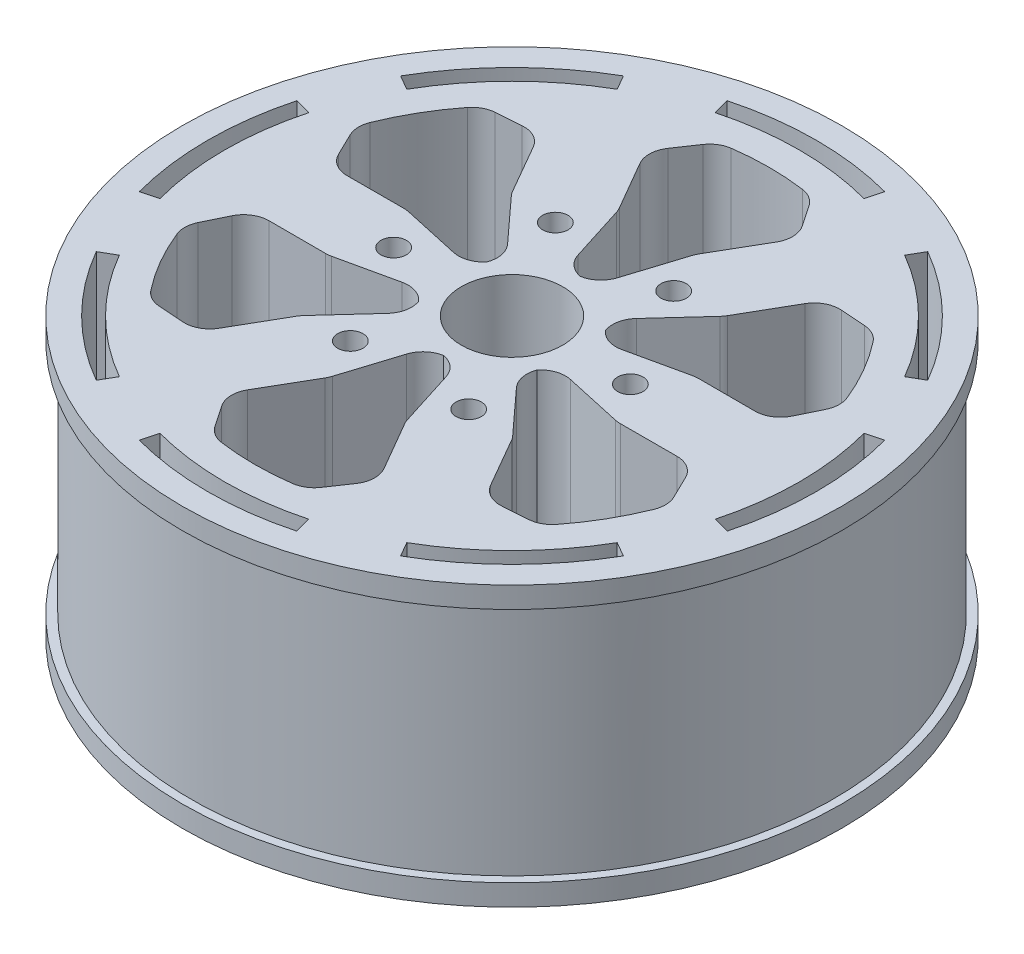
SolidWorks part; units mm, degrees
material "环氧树脂,未充填"
ref_plane "前视基准面" through (0, 0, 0) normal (0, 0, 1) x (1, 0, 0)
ref_plane "上视基准面" through (0, 0, 0) normal (0, 1, 0) x (1, 0, 0)
ref_plane "右视基准面" through (0, 0, 0) normal (1, 0, 0) x (0, 0, -1)
other "Configuration Table"
sketch "草图1" plane through (0, 0, 0) normal (0, 1, 0) x (1, 0, 0)
  circle A1 centre (0, 0) radius 38
extrude "凸台-拉伸1" add sketch "草图1" along normal blind 33
sketch "草图8" plane through (0, 0, 0) normal (0, -1, 0) x (1, 0, 0)
  circle A0 centre (0, 0) radius 39
extrude "凸台-拉伸2" add sketch "草图8" against normal blind 2.5
sketch "草图9" plane through (0, 33, 0) normal (0, 1, 0) x (1, 0, 0)
  circle A0 centre (0, 0) radius 39
extrude "凸台-拉伸3" add sketch "草图9" against normal blind 2.5
sketch "草图2" plane through (0, 0, 0) normal (0, -1, 0) x (1, 0, 0)
  circle A0 centre (0, 0) radius 32.5
extrude "切除-拉伸1" cut sketch "草图2" against normal blind 15.2
sketch "草图3" plane through (0, 33, 0) normal (0, 1, 0) x (1, 0, 0)
  line L0 (239.7439, 493.986) -> (1239.7439, 493.986) construction
  line L1 (0, 8) -> (0, 29.9069) construction
  line L3 (-5.5562, 29.9248) -> (-9.0065, 24.8288)
  line L6 (5.5562, 29.9248) -> (9.0065, 24.8288)
  line L45 (-1.6237, 7.8955) -> (-4.546, 17.1272)
  line L46 (-4.546, 17.1272) -> (-9.0065, 24.8288)
  line L47 (4.546, 17.1272) -> (9.0065, 24.8288)
  line L48 (1.6237, 7.8955) -> (4.546, 17.1272)
  line L49 (17.1056, 4.6266) -> (26.0056, 4.6146)
  line L50 (28.6937, 10.1506) -> (26.0056, 4.6146)
  line L52 (23.1376, 19.7742) -> (16.9991, 20.2143)
  line L53 (12.5596, 12.5006) -> (16.9991, 20.2143)
  line L54 (6.0258, 5.3539) -> (12.5596, 12.5006)
  line L55 (7.6496, 2.5416) -> (17.1056, 4.6266)
  line L56 (12.5596, -12.5006) -> (16.9991, -20.2143)
  line L57 (23.1376, -19.7742) -> (16.9991, -20.2143)
  line L59 (28.6937, -10.1506) -> (26.0056, -4.6146)
  line L60 (17.1056, -4.6266) -> (26.0056, -4.6146)
  line L61 (7.6496, -2.5416) -> (17.1056, -4.6266)
  line L62 (6.0258, -5.3539) -> (12.5596, -12.5006)
  line L63 (-4.546, -17.1272) -> (-9.0065, -24.8288)
  line L64 (-5.5562, -29.9248) -> (-9.0065, -24.8288)
  line L66 (5.5562, -29.9248) -> (9.0065, -24.8288)
  line L67 (4.546, -17.1272) -> (9.0065, -24.8288)
  line L68 (1.6237, -7.8955) -> (4.546, -17.1272)
  line L69 (-1.6237, -7.8955) -> (-4.546, -17.1272)
  line L70 (-17.1056, -4.6266) -> (-26.0056, -4.6146)
  line L71 (-28.6937, -10.1506) -> (-26.0056, -4.6146)
  line L73 (-23.1376, -19.7742) -> (-16.9991, -20.2143)
  line L74 (-12.5596, -12.5006) -> (-16.9991, -20.2143)
  line L75 (-6.0258, -5.3539) -> (-12.5596, -12.5006)
  line L76 (-7.6496, -2.5416) -> (-17.1056, -4.6266)
  line L77 (-12.5596, 12.5006) -> (-16.9991, 20.2143)
  line L78 (-23.1376, 19.7742) -> (-16.9991, 20.2143)
  line L80 (-28.6937, 10.1506) -> (-26.0056, 4.6146)
  line L81 (-17.1056, 4.6266) -> (-26.0056, 4.6146)
  line L82 (-7.6496, 2.5416) -> (-17.1056, 4.6266)
  line L83 (-6.0258, 5.3539) -> (-12.5596, 12.5006)
  circle A4 centre (0, 0) radius 32.35 construction
  arc A10 (1.6237, 7.8955) -> (-1.6237, 7.8955) centre (0, 0) ccw
  circle A11 centre (0, 0) radius 6
  arc A12 (7.6496, 2.5416) -> (6.0258, 5.3539) centre (0, 0) ccw
  arc A13 (6.0258, -5.3539) -> (7.6496, -2.5416) centre (0, 0) ccw
  arc A14 (-1.6237, -7.8955) -> (1.6237, -7.8955) centre (0, 0) ccw
  arc A15 (-7.6496, -2.5416) -> (-6.0258, -5.3539) centre (0, 0) ccw
  arc A16 (-6.0258, 5.3539) -> (-7.6496, 2.5416) centre (0, 0) ccw
  arc A17 (-23.1376, 19.7742) -> (-28.6937, 10.1506) centre (0, 0) ccw
  arc A18 (-28.6937, -10.1506) -> (-23.1376, -19.7742) centre (0, 0) ccw
  arc A19 (-5.5562, -29.9248) -> (5.5562, -29.9248) centre (0, 0) ccw
  arc A20 (23.1376, -19.7742) -> (28.6937, -10.1506) centre (0, 0) ccw
  arc A21 (28.6937, 10.1506) -> (23.1376, 19.7742) centre (0, 0) ccw
  arc A22 (5.5562, 29.9248) -> (-5.5562, 29.9248) centre (0, 0) ccw
  circle A31 centre (-7, 12.1244) radius 1.5
  circle A32 centre (7, 12.1244) radius 1.5
  circle A33 centre (14, 0) radius 1.5
  circle A34 centre (7, -12.1244) radius 1.5
  circle A35 centre (-7, -12.1244) radius 1.5
  circle A36 centre (-14, 0) radius 1.5
  point P8 (0.0448, 0.0448)
  point P23 (0, 29.9248)
  point P67 (0.0399, 0.0329)
  point P68 (0, 0)
  point P74 (0, 0)
  point P82 (0, 0)
  dimension "D1" = 6
  dimension "D2" = 6
extrude "切除-拉伸2" cut sketch "草图3" against normal through all
ref_axis "基准轴2" through (0, 15.2, 0) along (0, 1, 0)
sketch "草图7" plane through (0, 0, 0) normal (0, -1, 0) x (1, 0, 0)
  line L0 (-8.7998, 32.8415) -> (-9.3175, 34.7733)
  line L1 (0, 0) -> (0, 43.8624) construction
  line L2 (8.7998, 32.8415) -> (9.3175, 34.7733)
  line L3 (17, 29.4449) -> (18, 31.1769)
  line L4 (29.4449, 17) -> (31.1769, 18)
  line L5 (32.8415, 8.7998) -> (34.7733, 9.3175)
  line L6 (32.8415, -8.7998) -> (34.7733, -9.3175)
  line L7 (29.4449, -17) -> (31.1769, -18)
  line L8 (17, -29.4449) -> (18, -31.1769)
  line L9 (8.7998, -32.8415) -> (9.3175, -34.7733)
  line L10 (-8.7998, -32.8415) -> (-9.3175, -34.7733)
  line L11 (-17, -29.4449) -> (-18, -31.1769)
  line L12 (-29.4449, -17) -> (-31.1769, -18)
  line L13 (-32.8415, -8.7998) -> (-34.7733, -9.3175)
  line L14 (-32.8415, 8.7998) -> (-34.7733, 9.3175)
  line L15 (-29.4449, 17) -> (-31.1769, 18)
  line L16 (-17, 29.4449) -> (-18, 31.1769)
  arc A0 (8.7998, 32.8415) -> (-8.7998, 32.8415) centre (0, 0) ccw
  arc A1 (9.3175, 34.7733) -> (-9.3175, 34.7733) centre (0, 0) ccw
  arc A2 (29.4449, 17) -> (17, 29.4449) centre (0, 0) ccw
  arc A3 (31.1769, 18) -> (18, 31.1769) centre (0, 0) ccw
  arc A4 (32.8415, -8.7998) -> (32.8415, 8.7998) centre (0, 0) ccw
  arc A5 (34.7733, -9.3175) -> (34.7733, 9.3175) centre (0, 0) ccw
  arc A6 (17, -29.4449) -> (29.4449, -17) centre (0, 0) ccw
  arc A7 (18, -31.1769) -> (31.1769, -18) centre (0, 0) ccw
  arc A8 (-8.7998, -32.8415) -> (8.7998, -32.8415) centre (0, 0) ccw
  arc A9 (-9.3175, -34.7733) -> (9.3175, -34.7733) centre (0, 0) ccw
  arc A10 (-29.4449, -17) -> (-17, -29.4449) centre (0, 0) ccw
  arc A11 (-31.1769, -18) -> (-18, -31.1769) centre (0, 0) ccw
  arc A12 (-32.8415, 8.7998) -> (-32.8415, -8.7998) centre (0, 0) ccw
  arc A13 (-34.7733, 9.3175) -> (-34.7733, -9.3175) centre (0, 0) ccw
  arc A14 (-17, 29.4449) -> (-29.4449, 17) centre (0, 0) ccw
  arc A15 (-18, 31.1769) -> (-31.1769, 18) centre (0, 0) ccw
  point P39 (0, 0)
  dimension "D1" = 8
extrude "切除-拉伸3" cut sketch "草图7" against normal through all
fillet "圆角5" radius 3 48 edges at (7.6496, 24.1, -2.5416) (6.0258, 24.1, -5.3539) (12.5596, 24.1, -12.5006) (16.9991, 24.1, -20.2143) (23.1376, 24.1, -19.7742) (28.6937, 24.1, -10.1506) (26.0056, 24.1, -4.6146) (17.1056, 24.1, -4.6266) (12.5596, 24.1, 12.5006) (16.9991, 24.1, 20.2143) (23.1376, 24.1, 19.7742) (28.6937, 24.1, 10.1506) (17.1056, 24.1, 4.6266) (7.6496, 24.1, 2.5416) (6.0258, 24.1, 5.3539) (26.0056, 24.1, 4.6146) (-4.546, 24.1, 17.1272) (-5.5562, 24.1, 29.9248) (5.5562, 24.1, 29.9248) (9.0065, 24.1, 24.8288) (4.546, 24.1, 17.1272) (1.6237, 24.1, 7.8955) (-1.6237, 24.1, 7.8955) (-9.0065, 24.1, 24.8288) (-17.1056, 24.1, 4.6266) (-28.6937, 24.1, 10.1506) (-23.1376, 24.1, 19.7742) (-16.9991, 24.1, 20.2143) (-12.5596, 24.1, 12.5006) (-6.0258, 24.1, 5.3539) (-7.6496, 24.1, 2.5416) (-26.0056, 24.1, 4.6146) (-12.5596, 24.1, -12.5006) (-23.1376, 24.1, -19.7742) (-28.6937, 24.1, -10.1506) (-26.0056, 24.1, -4.6146) (-17.1056, 24.1, -4.6266) (-7.6496, 24.1, -2.5416) (-6.0258, 24.1, -5.3539) (-16.9991, 24.1, -20.2143) (4.546, 24.1, -17.1272) (5.5562, 24.1, -29.9248) (-5.5562, 24.1, -29.9248) (-9.0065, 24.1, -24.8288) (-4.546, 24.1, -17.1272) (-1.6237, 24.1, -7.8955) (1.6237, 24.1, -7.8955) (9.0065, 24.1, -24.8288)
sketch "草图10" plane through (0, 33, 0) normal (0, 1, 0) x (1, 0, 0)
  circle A0 centre (0, 0) radius 20
